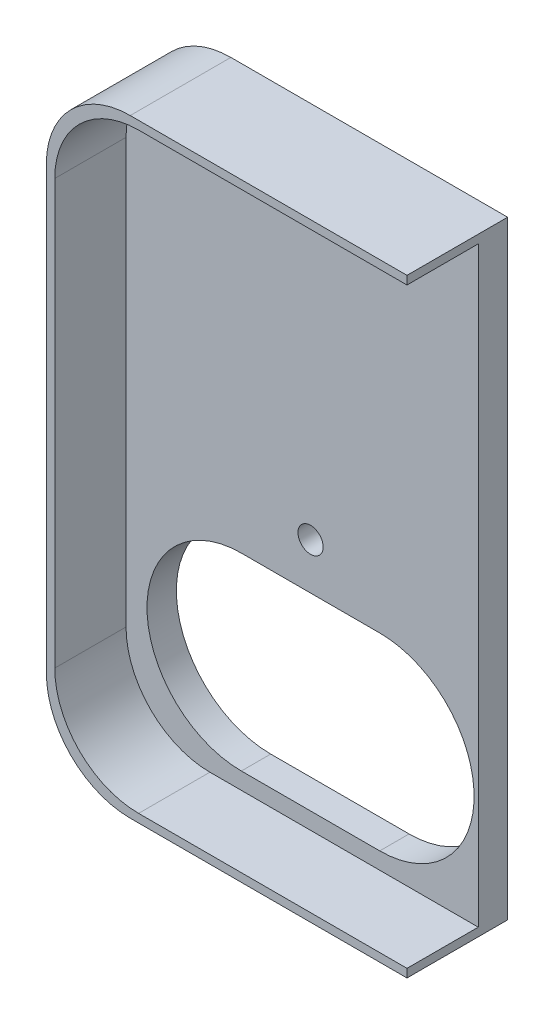
SolidWorks part; units mm, degrees
ref_plane "Front Plane" through (0, 0, 0) normal (1, 0, 0) x (0, 1, 0)
ref_plane "Top Plane" through (0, 0, 0) normal (0, 0, 1) x (0, 1, 0)
ref_plane "Right Plane" through (0, 0, 0) normal (0, 1, 0) x (-1, 0, 0)
sketch "Sketch2" plane through (0, 0, 0) normal (0, 0, 1) x (0, 1, 0)
  line L1 (-36.28, -21.5) -> (36.28, -21.5)
  line L2 (-36.28, -21.5) -> (-36.28, 11.5)
  line L3 (-26.28, 21.5) -> (26.28, 21.5)
  line L4 (36.28, -21.5) -> (36.28, 11.5)
  line L5 (-36.28, -21.5) -> (36.28, 21.5) construction
  line L6 (-36.28, 21.5) -> (36.28, -21.5) construction
  arc A0 (26.28, 21.5) -> (36.28, 11.5) centre (26.28, 11.5) cw
  arc A1 (-26.28, 21.5) -> (-36.28, 11.5) centre (-26.28, 11.5) ccw
  point P1 (0, 0)
  point P6 (0, 0)
  point P8 (0, 0)
  point P9 (0, 0)
  point P27 (0, 0)
  point P28 (0, 0)
  point P29 (0, 0)
  point P30 (0, 0)
  point P31 (-36.28, 11.5)
  dimension "D5" = 10
  dimension "D1" = 72.56
  dimension "D2" = 43
extrude "Boss-Extrude2" add sketch "Sketch2" along normal blind 12 contours L1 L4 A0 L3 A1 L2 region at (0.2687, 0, 0)
sketch "Sketch5" plane through (0, 0, 12) normal (0, 0, 1) x (1, 0, 0)
  line L0 (21.5, -36.28) -> (21.5, 36.28) construction
  line L1 (21.5, -35.28) -> (-10.5, -35.28)
  line L2 (21.5, -35.28) -> (21.5, 35.28)
  line L3 (21.5, 35.28) -> (-10.5, 35.28)
  line L4 (-20.5, -25.28) -> (-20.5, 25.28)
  line L5 (21.5, 36.28) -> (-11.5, 36.28) construction
  line L6 (21.5, -36.28) -> (-11.5, -36.28) construction
  line L7 (-21.5, -26.28) -> (-21.5, 26.28) construction
  arc A0 (-10.5, -35.28) -> (-20.5, -25.28) centre (-10.5, -25.28) cw
  arc A1 (-10.5, 35.28) -> (-20.5, 25.28) centre (-10.5, 25.28) ccw
  dimension "D4" = 10
  dimension "D1" = 1
  dimension "D2" = 1
  dimension "D3" = 1
extrude "Cut-Extrude1" cut sketch "Sketch5" against normal blind 8.5
sketch "Sketch6" plane through (0, 0, 3.5) normal (0, 0, 1) x (1, 0, 0)
  line L1 (9.75, -33.28) -> (-6.75, -33.28)
  line L3 (9.75, -10.78) -> (-6.75, -10.78)
  line L5 (-10.5, -35.28) -> (21.5, -35.28) construction
  line L6 (-20.5, 25.28) -> (-20.5, -25.28) construction
  line L7 (-18, -22.03) -> (21, -22.03) construction
  arc A0 (-6.75, -33.28) -> (-6.75, -10.78) centre (-6.75, -22.03) cw
  arc A1 (9.75, -10.78) -> (9.75, -33.28) centre (9.75, -22.03) cw
  circle A2 centre (1.5, -5.28) radius 1.5
  point P6 (-18, -22.03)
  point P7 (21, -22.03)
  point P14 (1.5, -5.28)
  dimension "D1" = 39
  dimension "D2" = 22.5
  dimension "D3" = 2
  dimension "D4" = 2.5
  dimension "D5" = 30
extrude "Cut-Extrude2" cut sketch "Sketch6" against normal blind 8.5
